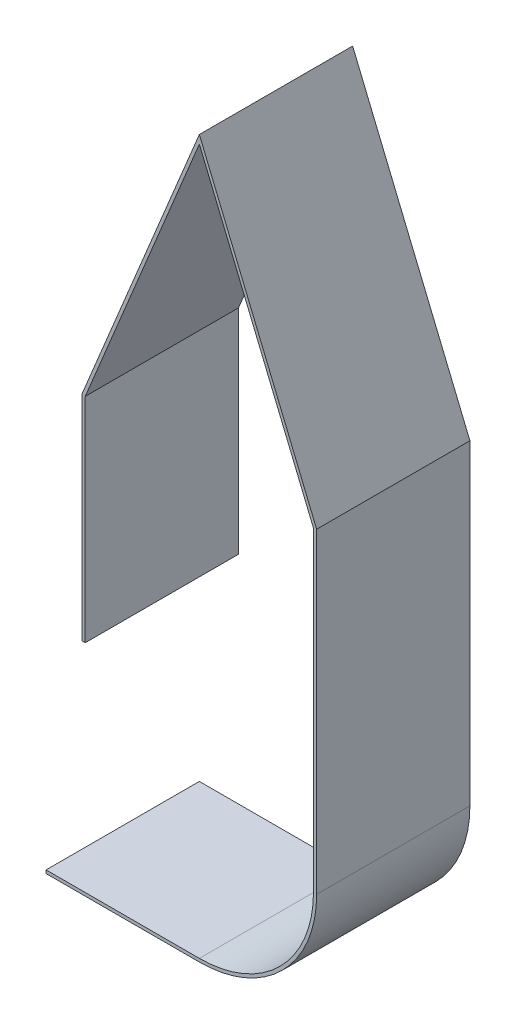
SolidWorks part; units mm, degrees
ref_plane "Front Plane" through (0, 0, 0) normal (0, 0, 1) x (1, 0, 0)
ref_plane "Top Plane" through (0, 0, 0) normal (0, 1, 0) x (1, 0, 0)
ref_plane "Right Plane" through (0, 0, 0) normal (1, 0, 0) x (0, 0, -1)
ref_axis "Axis1" through (0, 0, -3.81) along (0, 0, 1)
ref_axis "Axis2" through (-82.926, 0, 0) along (1, 0, 0)
ref_plane "Plane1" through (0, 0, 0) normal (0, -0.5, -0.866) x (1, 0, 0)
ref_plane "Plane2" through (0, -38.1, -65.9911) normal (0, -0.5, -0.866) x (1, 0, 0)
sketch "Sketch2" plane through (0, 0, 0) normal (0, 0, 1) x (1, 0, 0)
  line L0 (0, 0) -> (0, -254) construction
  line L1 (0, 0) -> (58.321, -140.7992)
  line L2 (0, 0) -> (-58.321, -140.7992)
  line L3 (-58.321, -140.7992) -> (-58.321, -247.2138)
  line L5 (0, 0) -> (0, -254) construction
  line L6 (58.321, -247.2138) -> (58.321, -140.7992)
  line L7 (58.321, -247.2138) -> (58.321, -298.0138)
  line L8 (-76.2, -356.3348) -> (0, -356.3348)
  line L9 (-76.2, -354.7473) -> (0, -354.7473)
  line L10 (56.7335, -247.2138) -> (56.7335, -298.0138)
  line L11 (56.7335, -247.2138) -> (56.7335, -141.115)
  line L12 (0, -4.1483) -> (56.7335, -141.115)
  line L13 (0, -4.1483) -> (-56.7335, -141.115)
  line L14 (-56.7335, -141.115) -> (-56.7335, -247.2138)
  line L15 (-56.7335, -247.2138) -> (-58.321, -247.2138)
  line L16 (-76.2, -354.7473) -> (-76.2, -356.3348)
  circle A0 centre (0, 0) radius 254 construction
  circle A1 centre (0, 0) radius 152.4 construction
  arc A2 (58.321, -298.0138) -> (0, -356.3348) centre (0, -298.0138) cw
  arc A3 (56.7335, -298.0138) -> (0, -354.7473) centre (0, -298.0138) cw
  dimension "D2" = 304.8
  dimension "D6" = 1.5875
  dimension "D1" = 254
  dimension "D3" = 50.8
  dimension "D4" = 76.2
  dimension "D5" = 45
extrude "Boss-Extrude1" add sketch "Sketch2" against normal blind 76.2
ref_axis "Axis3" through (0, 0, -76.2) along (0, -0.5, -0.866)
ref_plane "Plane3" through (0, 0, 0) normal (0, 0.866, -0.5) x (1, 0, 0)
sketch "Sketch3" plane through (0, 0, 0) normal (0, 0.866, -0.5) x (1, 0, 0)
  line L0 (-76.2, 76.2) -> (-38.1, 66.9925)
  line L1 (81.3852, 76.2) -> (-81.3852, 76.2) construction
  line L2 (-76.2, 243.3648) -> (-76.2, 177.3736) construction
  line L3 (-38.1, 66.9925) -> (-76.2, 57.785)
  line L4 (-76.2, 57.785) -> (-38.1, 48.5775)
  line L5 (-38.1, 48.5775) -> (-76.2, 39.37)
  line L6 (-76.2, 39.37) -> (-38.1, 30.1625)
  line L7 (-38.1, 30.1625) -> (-76.2, 20.955)
  line L8 (-76.2, 20.955) -> (-38.4295, 10.4775)
  line L9 (-38.4295, 10.4775) -> (-76.2, 0)
  line L10 (81.3852, 0) -> (-81.3852, 0) construction
  line L11 (-76.2, 0) -> (-83.7856, 0)
  line L12 (-82.926, 0) -> (65.047, 0) construction
  line L13 (-83.7856, 0) -> (-83.7856, 76.2)
  line L14 (-83.7856, 76.2) -> (-76.2, 76.2)
  dimension "D1" = 18.415
  dimension "D2" = 18.415
  dimension "D3" = 18.415
  dimension "D4" = 38.1
extrude "Cut-Extrude4" [suppressed] cut sketch "Sketch3" against normal up to surface (367.4659 mm away) from surface
